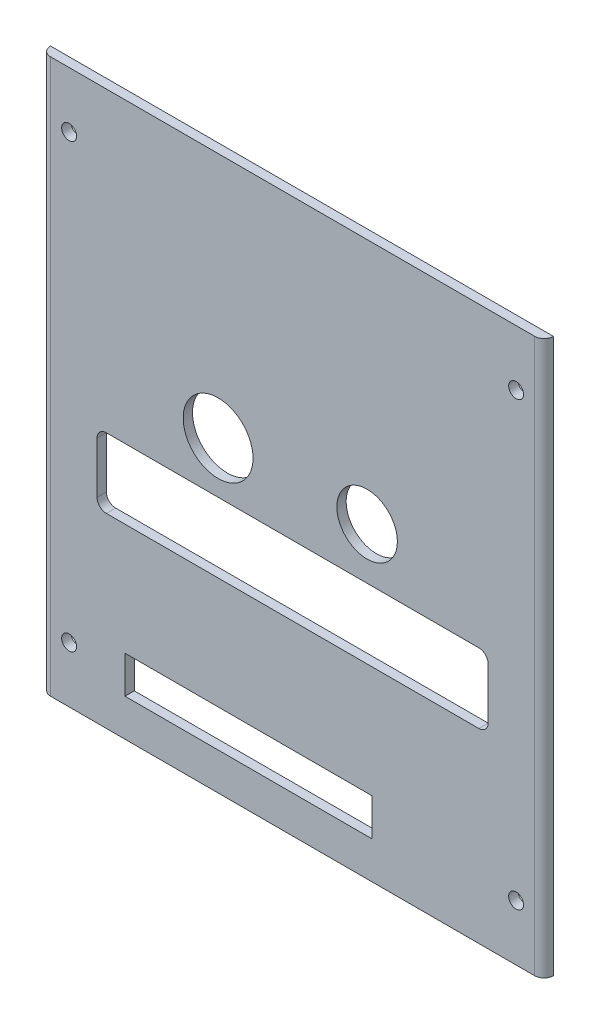
SolidWorks part; units mm, degrees
ref_plane "Płaszczyzna przednia" through (0, 0, 0) normal (0, 0, 1) x (1, 0, 0)
ref_plane "Płaszczyzna górna" through (0, 0, 0) normal (0, 1, 0) x (1, 0, 0)
ref_plane "Płaszczyzna prawa" through (0, 0, 0) normal (1, 0, 0) x (0, 0, -1)
sketch "Szkic1" plane through (0, 0, 0) normal (0, 0, 1) x (1, 0, 0)
  line L1 (4, 0) -> (108, 0)
  line L2 (4, 0) -> (4, 118.94)
  line L3 (4, 118.94) -> (108, 118.94)
  line L4 (108, 0) -> (108, 118.94)
extrude "Dodanie-wyciągnięcie1" add sketch "Szkic1" along normal blind 2
sketch "Szkic2" plane through (0, 0, 0) normal (0, 0, -1) x (-1, 0, 0)
  line L0 (-18, 8) -> (-94, 8) construction
  line L1 (-100, 8) -> (-12, 8)
  line L2 (-100, 8) -> (-100, 16.0073)
  line L3 (-100, 16.0073) -> (-12, 16.0073)
  line L4 (-12, 8) -> (-12, 16.0073)
  line L5 (-12, 94.64) -> (-12, 48) construction
  line L6 (-95.9385, 9.6) -> (-95.9385, 8) construction
  line L7 (-100, 8) -> (-12, 8)
  line L8 (-100, 8) -> (-100, 9.6)
  line L9 (-100, 9.6) -> (-12, 9.6)
  line L10 (-12, 8) -> (-12, 9.6)
  line L11 (-20, 12.8037) -> (-12, 12.8037) construction
  line L12 (-12, 9.6) -> (-20, 9.6)
  line L13 (-12, 9.6) -> (-12, 16.0073)
  line L14 (-12, 16.0073) -> (-20, 16.0073)
  line L15 (-20, 9.6) -> (-20, 16.0073)
  line L16 (-73, 12.8037) -> (-20, 12.8037) construction
  line L17 (-20, 9.6) -> (-73, 9.6)
  line L18 (-20, 9.6) -> (-20, 16.0073)
  line L19 (-20, 16.0073) -> (-73, 16.0073)
  line L20 (-73, 9.6) -> (-73, 16.0073)
  line L22 (-73, 9.6) -> (-20, 9.6)
  line L23 (-73, 9.6) -> (-73, 8)
  line L24 (-73, 8) -> (-20, 8)
  line L25 (-20, 9.6) -> (-20, 8)
extrude "Wytnij-wyciągnięcie2" cut sketch "Szkic2" against normal blind 2 contours L25 L9 L23 L7 | L20 L9 L15 L3 region at (46.5, 8.8, 0) region at (46.5, 12.8037, 0)
sketch "Szkic4" plane through (0, 0, 0) normal (0, 0, -1) x (-1, 0, 0)
  line L0 (-2, 116.94) -> (-4, 118.94)
  line L1 (-2, 116.94) -> (-4, 116.94)
  line L2 (-2, 116.94) -> (-2, 0)
  line L3 (-2, 0) -> (-4, 0)
  line L4 (-4, 116.94) -> (-4, 0)
  line L5 (-108, 0) -> (-110, 0)
  line L6 (-108, 0) -> (-108, 116.94)
  line L7 (-108, 116.94) -> (-110, 116.94)
  line L8 (-110, 0) -> (-110, 116.94)
  line L9 (-4, 118.94) -> (-4, 116.94)
  line L10 (-108, 116.94) -> (-108, 118.94)
  line L11 (-108, 118.94) -> (-110, 116.94)
  line L13 (-108, 118.94) -> (-110, 118.94)
  line L14 (-108, 118.94) -> (-108, 116.94)
  line L15 (-108, 116.94) -> (-110, 116.94)
  line L16 (-110, 118.94) -> (-110, 116.94)
  line L17 (-4, 118.94) -> (-2, 118.94)
  line L18 (-4, 118.94) -> (-4, 116.94)
  line L19 (-4, 116.94) -> (-2, 116.94)
  line L20 (-2, 118.94) -> (-2, 116.94)
extrude "Dodanie-wyciągnięcie2" add sketch "Szkic4" against normal blind 2 contours L1 L0 L8 | L3 L2 L1 L8 | L10 L11 L7 | L8 L5 L10 L7 | L14 L13 L16 L15 | L18 L17 L20 L19 region at (3.3333, 117.6067, 0) region at (3, 58.47, 0) region at (109, 58.47, 0) region at (108.6667, 117.6067, 0)
sketch "Szkic5" plane through (0, 0, 2) normal (0, 0, 1) x (1, 0, 0)
  line L0 (4, 16) -> (12, 16) construction
  line L1 (100, 8) -> (108, 16) construction
  line L2 (108, 118.94) -> (108, 0) construction
  line L3 (12, 118.94) -> (4, 118.94) construction
  line L4 (4, 8) -> (108, 8) construction
  line L5 (12, 8) -> (12, 118.94) construction
  line L6 (110, 118.94) -> (2, 118.94) construction
  line L7 (108, 118.94) -> (100, 118.94) construction
  line L8 (100, 118.94) -> (100, 8) construction
  line L9 (4, 8) -> (4, 16) construction
  line L10 (12, 16) -> (100, 16) construction
  line L11 (100, 16) -> (108, 16) construction
  line L12 (4, 118.94) -> (4, 0) construction
  line L13 (4, 16) -> (12, 8) construction
  line L14 (12, 110.94) -> (4, 110.94) construction
  line L15 (8, 110.94) -> (8, 102.94) construction
  line L16 (12, 110.94) -> (100, 110.94) construction
  line L17 (4, 102.94) -> (12, 102.94) construction
  line L18 (12, 102.94) -> (100, 102.94) construction
  line L19 (100, 102.94) -> (108, 102.94) construction
  line L20 (100, 110.94) -> (108, 110.94) construction
  line L21 (104, 110.94) -> (104, 102.94) construction
  circle A0 centre (8, 12) radius 1.6
  circle A1 centre (104, 12) radius 1.6
  circle A2 centre (8, 106.94) radius 1.6
  circle A3 centre (104, 106.94) radius 1.6
extrude "Wytnij-wyciągnięcie3" cut sketch "Szkic5" against normal blind 2
fillet "Zaokrąglenie1" radius 2 2 edges at (110, 59.47, 2) (2, 59.47, 2)
sketch "Szkic6" plane through (0, 0, 2) normal (0, 0, 1) x (1, 0, 0)
  line L0 (56, 0) -> (40, 0) construction
  line L1 (4, 0) -> (108, 0) construction
  line L2 (56, 0) -> (72, 0) construction
  line L3 (72, 0) -> (72, 66) construction
  line L4 (40, 0) -> (40, 66) construction
  circle A0 centre (72, 66) radius 6.5
  circle A1 centre (40, 66) radius 7.5
extrude "Wytnij-wyciągnięcie4" cut sketch "Szkic6" against normal blind 12
sketch "Szkic7" plane through (0, 0, 2) normal (0, 0, 1) x (1, 0, 0)
  line L0 (56, 0) -> (56, 49) construction
  line L1 (4, 0) -> (108, 0) construction
  line L2 (56, 49) -> (56, 55) construction
  line L3 (56, 55) -> (98, 55)
  line L4 (98, 55) -> (98, 40)
  line L5 (98, 40) -> (14, 40)
  line L6 (14, 40) -> (14, 55)
  line L7 (14, 55) -> (56, 55)
extrude "Wytnij-wyciągnięcie5" cut sketch "Szkic7" against normal blind 12
fillet "Zaokrąglenie2" radius 2 4 edges at (98, 40, 1) (98, 55, 1) (14, 55, 1) (14, 40, 1)
